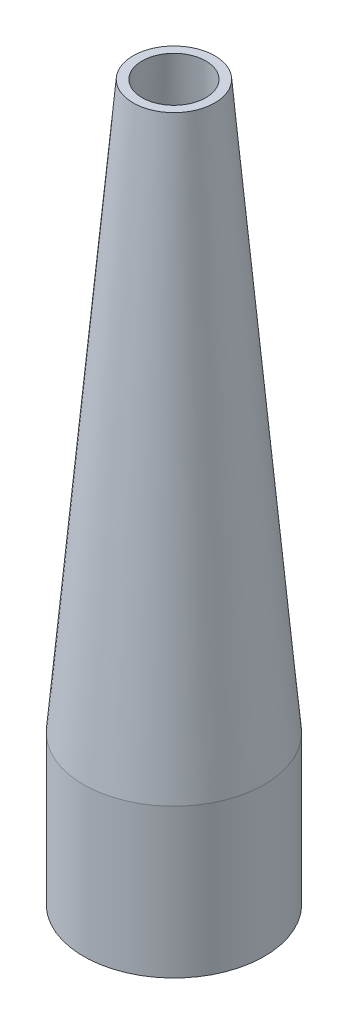
SolidWorks part; units mm, degrees
material "S-Glass Fiber"
ref_plane "Front Plane" through (0, 0, 0) normal (0, 0, 1) x (1, 0, 0)
ref_plane "Top Plane" through (0, 0, 0) normal (0, 1, 0) x (1, 0, 0)
ref_plane "Right Plane" through (0, 0, 0) normal (1, 0, 0) x (0, 0, -1)
sketch "Sketch1" plane through (0, 0, 0) normal (0, 0, 1) x (1, 0, 0)
  line L0 (0, 0) -> (0, 49.1635) construction
  line L1 (9.525, 49.1635) -> (12.2022, 49.1635)
  line L2 (12.2022, 49.1635) -> (26.9875, -119.8334)
  line L3 (26.9875, -119.8334) -> (24.3103, -119.8334)
  line L4 (24.3103, -119.8334) -> (9.525, 49.1635)
  line L5 (26.9875, -164.2834) -> (26.9875, -167.4584) construction
  line L6 (24.3103, -119.8334) -> (26.9875, -119.8334)
  line L7 (24.3103, -119.8334) -> (24.3103, -164.2834)
  line L8 (24.3103, -164.2834) -> (26.9875, -164.2834)
  line L9 (26.9875, -119.8334) -> (26.9875, -164.2834)
revolve "Revolve1" add sketch "Sketch1" angle 360 about L0 region at (18.2563, -35.335, 0) region at (25.6489, -142.0584, 0)
